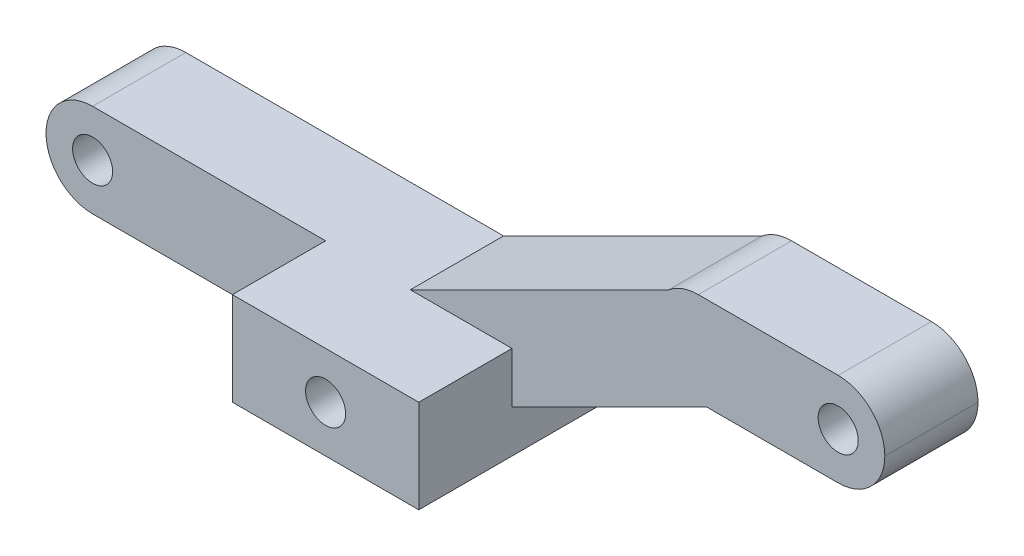
SolidWorks part; units mm, degrees
ref_plane "정면" through (0, 0, 0) normal (0, 0, 1) x (1, 0, 0)
ref_plane "윗면" through (0, 0, 0) normal (0, 1, 0) x (1, 0, 0)
ref_plane "우측면" through (0, 0, 0) normal (1, 0, 0) x (0, 0, -1)
sketch "스케치2" plane through (0, 0, 0) normal (0, 0, 1) x (1, 0, 0)
  line L0 (70, 27.5) -> (70, 17.5)
  line L1 (-20, 12.5) -> (19.0949, 12.5)
  line L2 (-20, 12.5) -> (-20, 2.5)
  line L3 (-20, 2.5) -> (20, 2.5)
  line L7 (50, 27.5) -> (70, 27.5)
  line L9 (50.9051, 17.5) -> (70, 17.5)
  line L13 (23.2009, 3.6589) -> (50.9051, 17.5)
  line L14 (19.0949, 12.5) -> (46.7991, 26.3411)
  arc A2 (20, 2.5) -> (23.2009, 3.6589) centre (20, 7.5) ccw
  arc A3 (50, 27.5) -> (46.7991, 26.3411) centre (50, 22.5) ccw
  dimension "D1" = 5
  dimension "D7" = 5
  dimension "D2" = 90
  dimension "D3" = 10
  dimension "D4" = 5
  dimension "D6" = 10
extrude "보스-돌출1" add sketch "스케치2" along normal blind 10
sketch "스케치3" plane through (0, 0, 10) normal (0, 0, 1) x (1, 0, 0)
  line L0 (19.0949, 12.5) -> (-20, 12.5) construction
  line L1 (10, 12.5) -> (30, 12.5)
  line L2 (10, 12.5) -> (10, 2.5)
  line L3 (10, 2.5) -> (30, 2.5)
  line L4 (30, 12.5) -> (30, 2.5)
  line L5 (10, 12.5) -> (30, 2.5) construction
  line L6 (10, 2.5) -> (30, 12.5) construction
  dimension "D2" = 20
extrude "보스-돌출2" add sketch "스케치3" along normal blind 20 from surface starting at face at (31, 15, 0)
fillet "필렛1" radius 5 4 edges at (-20, 12.5, 5) (-20, 2.5, 5) (70, 17.5, 5) (70, 27.5, 5)
sketch "스케치5" plane through (0, 0, 20) normal (0, 0, 1) x (1, 0, 0)
  line L3 (65, 27.5) -> (50, 27.5) construction
  line L5 (30, 2.5) -> (30, 12.5) construction
  line L6 (19.0949, 12.5) -> (30, 12.5) construction
  circle A0 centre (20, 7.5) radius 2.15
  circle A1 centre (65, 22.5) radius 2.15
  circle A2 centre (-15, 7.5) radius 2.15
  dimension "D1" = 4.3
  dimension "D2" = 4.3
  dimension "D3" = 4.3
  dimension "D4" = 5
  dimension "D5" = 5
  dimension "D6" = 10
  dimension "D7" = 5
extrude "컷-돌출2" cut sketch "스케치5" against normal through all
sketch "스케치7" plane through (0, 2.5, 0) normal (0, -1, 0) x (1, 0, 0)
  line L0 (10, 20) -> (30, 20) construction
  line L1 (12.5, 17.5) -> (27.5, 17.5) construction
  line L2 (12.5, 17.5) -> (12.5, 2.5) construction
  line L3 (12.5, 2.5) -> (27.5, 2.5) construction
  line L4 (27.5, 17.5) -> (27.5, 2.5) construction
  line L5 (12.5, 17.5) -> (27.5, 2.5) construction
  line L6 (12.5, 2.5) -> (27.5, 17.5) construction
  line L7 (30, 20) -> (30, 0) construction
  circle A0 centre (12.5, 17.5) radius 1
  circle A1 centre (27.5, 17.5) radius 1
  circle A2 centre (27.5, 2.5) radius 1
  circle A3 centre (12.5, 2.5) radius 1
  point P0 (20, 10)
  dimension "D5" = 2
  dimension "D1" = 15
  dimension "D2" = 15
  dimension "D3" = 10
  dimension "D4" = 10
extrude "컷-돌출4" cut sketch "스케치7" against normal blind 8
sketch "스케치8" plane through (0, 2.5, 0) normal (0, -1, 0) x (1, 0, 0)
  line L0 (10, 20) -> (30, 20) construction
  line L1 (30, 20) -> (30, 0) construction
  circle A0 centre (20, 10) radius 5
  dimension "D1" = 10
  dimension "D2" = 10
  dimension "D3" = 10
extrude "컷-돌출5" cut sketch "스케치8" against normal blind 2
